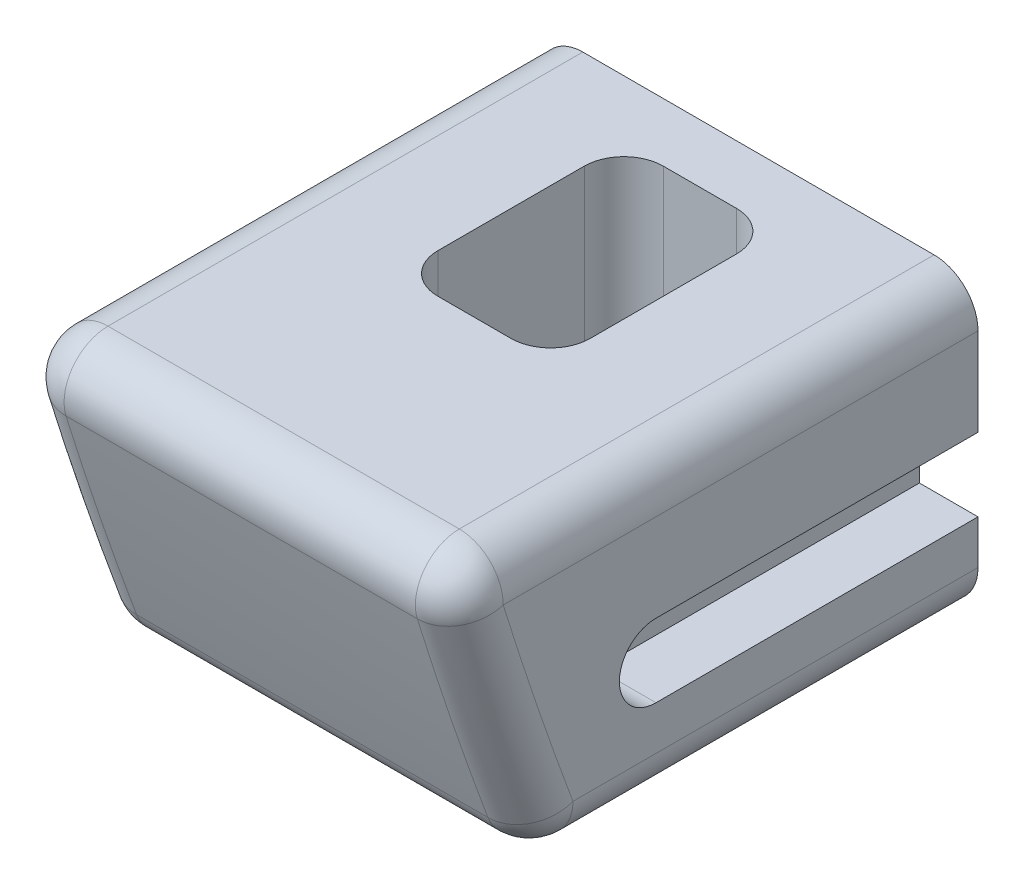
SolidWorks part; units mm, degrees
ref_plane "Front plane" through (0, 0, 0) normal (0, 0, 1) x (1, 0, 0)
ref_plane "Top plane" through (0, 0, 0) normal (0, 1, 0) x (1, 0, 0)
ref_plane "Right Plane" through (0, 0, 0) normal (1, 0, 0) x (0, 0, -1)
sketch "Sketch1" plane through (0, 0, 0) normal (0, 0, 1) x (1, 0, 0)
  line L1 (7.5, 0) -> (-7.5, 0)
  line L2 (7.5, 0) -> (7.5, 8)
  line L3 (7.5, 8) -> (-7.5, 8)
  line L4 (-7.5, 0) -> (-7.5, 8)
  point P4 (0, 0)
  dimension "D1" = 15
  dimension "D2" = 8
extrude "Boss-Extrude1" add sketch "Sketch1" along normal blind 10
sketch "Sketch2" plane through (0, 8, 0) normal (0, 1, 0) x (1, 0, 0)
  line L0 (-1.25, -2) -> (1.25, -2)
  line L1 (2.6, -3.35) -> (2.6, -8.35)
  line L2 (1.25, -9.7) -> (-1.25, -9.7)
  line L3 (-2.6, -8.35) -> (-2.6, -3.35)
  line L4 (7.5, 0) -> (-7.5, 0) construction
  arc A0 (1.25, -2) -> (2.6, -3.35) centre (1.25, -3.35) cw
  arc A1 (2.6, -8.35) -> (1.25, -9.7) centre (1.25, -8.35) cw
  arc A2 (-1.25, -9.7) -> (-2.6, -8.35) centre (-1.25, -8.35) cw
  arc A3 (-2.6, -3.35) -> (-1.25, -2) centre (-1.25, -3.35) cw
  point P12 (0, -2)
  dimension "D2" = 2.5
  dimension "D1" = 2
  dimension "D3" = 5
  dimension "D4" = 1.35
extrude "Cut-Extrude1" cut sketch "Sketch2" against normal through all
sketch "Sketch3" plane through (-7.5, 0, 0) normal (1, 0, 0) x (0, 0, -1)
  line L2 (-14.8733, -2) -> (0, -2)
  line L3 (0, -2) -> (0, 0)
  line L4 (-14.6479, 6.5) -> (-16.2187, 6.5)
  line L5 (1.25, 8) -> (-15.1071, 8)
  line L6 (0, 3.4) -> (0, 4.9638)
  line L7 (-14.3842, 1) -> (-10, 1)
  line L12 (0, 0) -> (-10, 0)
  line L37 (-10, 3.4) -> (0, 3.4)
  line L38 (-10, 8) -> (-10, 0) construction
  line L39 (-10, 1) -> (-10, 3.4)
  line L45 (4.2862, 4.9638) -> (1.25, 8)
  line L46 (4.2862, 4.9638) -> (1.25, 8)
  line L47 (0, 4.9638) -> (4.2862, 4.9638)
  line L48 (-10, 8) -> (-10, 0)
  line L50 (-10, 8) -> (-18.2355, 8)
  line L51 (0, 4.9638) -> (4.2862, 4.9638)
  line L83 (-10, 8) -> (0, 8) construction
  arc A1 (-16.2187, 6.5) -> (-14.3842, 1) centre (107.62, 44.75) ccw
  arc A2 (-16.6721, 8) -> (-13.2664, -2) centre (107.62, 44.75) ccw construction
  arc A3 (-18.2355, 8) -> (-14.8733, -2) centre (107.62, 44.75) ccw
  arc A4 (-17.8837, 6.816) -> (-14.2694, -3.5526) centre (107.62, 44.75) ccw construction
  arc A5 (-16.4479, 7.25) -> (-12.8749, -3) centre (107.62, 44.75) ccw construction
  arc A9 (-15.1071, 8) -> (-14.6479, 6.5) centre (107.62, 44.75) ccw
  line M6 (-14.3842, 1) -> (-10, 1)
  arc M10 (-16.2187, 6.5) -> (-14.3842, 1) centre (107.62, 44.75) ccw
  arc M17 (-15.1071, 8) -> (-14.6479, 6.5) centre (107.62, 44.75) ccw
  line M18 (-14.6479, 6.5) -> (-16.2187, 6.5)
  line M26 (-10, 1) -> (-10, 3.4)
  dimension "D2" = 2
  dimension "D1" = 0
  dimension "D3" = 1.5
extrude "Boss-Extrude2" add sketch "Sketch3" along normal up to vertex (15 mm away) contours A3 L2 L3 L12 M6 M10 M18 M17 | M26 M17 M18 M10 M6 | L50 A3 L2 L3 L12 L48 region at (-7.5, 0.7909, 10.5603) region at (-7.5, 4.5785, 12.6391) up to point (7.5, 0, 10)
sketch "Sketch7" plane through (0, 8, 0) normal (0, 1, 0) x (1, 0, 0)
  line L0 (-2.6, -11.2355) -> (-7.5, -11.2355)
  line L4 (-2.6, -3.35) -> (-2.6, -8.35)
  line L5 (1.25, -2) -> (-1.25, -2)
  line L6 (2.6, -8.35) -> (2.6, -3.35)
  line L7 (-1.25, -9.7) -> (1.25, -9.7)
  line L8 (-2.6, -11.2355) -> (-2.6, -8.35)
  line L10 (2.6, -8.35) -> (2.6, -11.2355)
  line L11 (-1.25, -9.7) -> (1.25, -9.7)
  line L12 (7.5, 0) -> (-7.5, 0)
  line L13 (-7.5, 0) -> (-7.5, -18.2355)
  line L14 (-7.5, -18.2355) -> (7.5, -18.2355)
  line L15 (7.5, -18.2355) -> (7.5, 0)
  line L16 (7.5, -11.2355) -> (2.6, -11.2355)
  line L17 (-7.5, -11.2355) -> (-7.5, -18.2355)
  line L19 (7.5, -18.2355) -> (7.5, -11.2355)
  line L22 (-7.5, -18.2355) -> (7.5, -18.2355)
  arc A4 (-1.25, -2) -> (-2.6, -3.35) centre (-1.25, -3.35) ccw
  arc A5 (2.6, -3.35) -> (1.25, -2) centre (1.25, -3.35) ccw
  arc A6 (1.25, -9.7) -> (2.6, -8.35) centre (1.25, -8.35) ccw
  arc A7 (-2.6, -8.35) -> (-1.25, -9.7) centre (-1.25, -8.35) ccw
  arc A10 (1.25, -9.7) -> (2.6, -8.35) centre (1.25, -8.35) ccw
  arc A11 (-2.6, -8.35) -> (-1.25, -9.7) centre (-1.25, -8.35) ccw
  dimension "D1" = 0
  dimension "D2" = 0
extrude "Boss-Extrude3" [suppressed] add sketch "Sketch7" along normal blind 15
draft "Draft1" [suppressed] type of draft neutral plane draft angle 15 faces to draft 2 parameters "D1"=15
fillet "Fillet2" [suppressed] radius 0.5
sketch "Sketch5" plane through (7.5, 0, 0) normal (1, 0, 0) x (0, 0, -1)
  line L0 (0, 1) -> (-11, 1)
  line L1 (0, -2) -> (0, 8) construction
  line L2 (-11, 3.5) -> (0, 3.5)
  line L3 (0, 3.5) -> (0, 1)
  line L5 (-18.2355, 8) -> (0, 8) construction
  arc A0 (-11, 1) -> (-11, 3.5) centre (-11, 2.25) cw
  dimension "D1" = 2.5
  dimension "D2" = 7
  dimension "D3" = 11
extrude "Cut-Extrude2" cut sketch "Sketch5" against normal blind 2
mirror "Mirror1" about plane through (0, 0, 0) normal (1, 0, 0) of "Cut-Extrude2"
sketch "Sketch6" plane through (0, 0, 0) normal (0, 1, 0) x (1, 0, 0)
  circle A0 centre (-1.25, -3.35) radius 0.8
  circle A2 centre (1.25, -3.35) radius 0.8
  circle A3 centre (1.25, -5.85) radius 0.8
  circle A4 centre (1.25, -8.35) radius 0.8
  circle A5 centre (-1.25, -5.85) radius 0.8
  circle A6 centre (-1.25, -8.35) radius 0.8
  arc A9 (1.25, -9.7) -> (2.6, -8.35) centre (1.25, -8.35) ccw construction
  dimension "D3" = 1.6
  dimension "D1" = 2
  dimension "D2" = 3
extrude "Cut-Extrude3" cut sketch "Sketch6" against normal through all both and the other way through all
fillet "Fillet1" radius 1.5 8 edges at (-7.5, 8, 9.1177) (7.5, 8, 9.1177) (-7.5, -2, 7.4366) (7.5, -2, 7.4366) (0, -2, 14.8733) (-7.5, 2.9662, 16.655) (7.5, 2.9662, 16.655) (0, 8, 18.2355)
